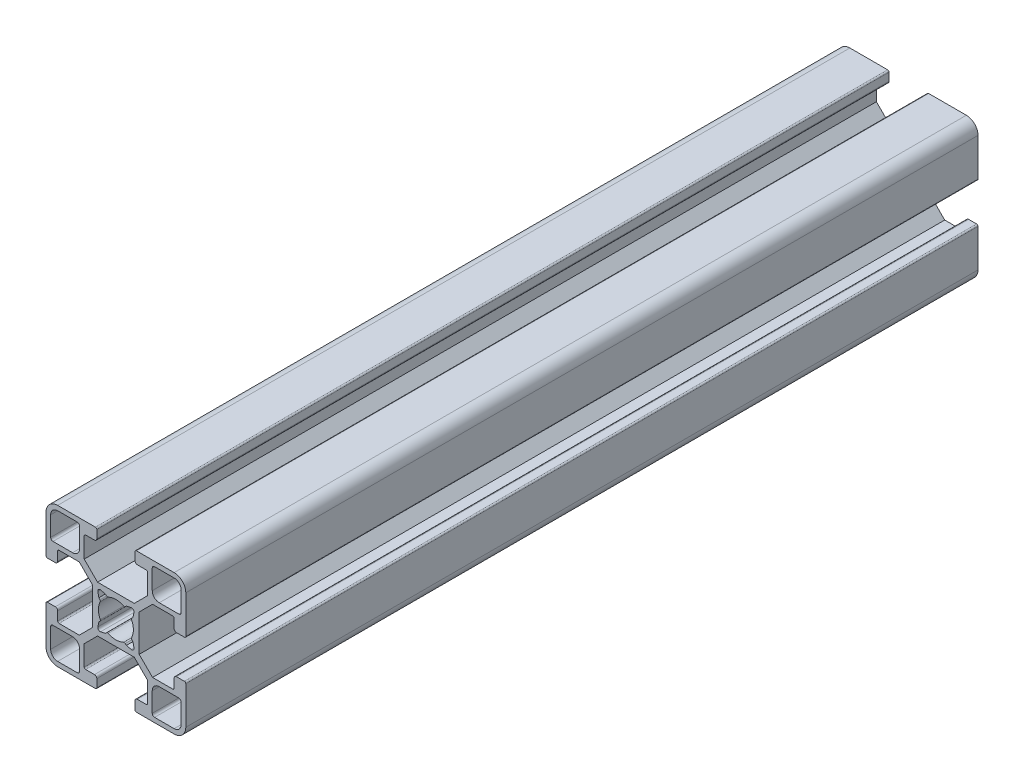
SolidWorks part; units mm, degrees
ref_plane "Front Plane" through (0, 0, 0) normal (0, 0, 1) x (1, 0, 0)
ref_plane "Top Plane" through (0, 0, 0) normal (0, 1, 0) x (1, 0, 0)
ref_plane "Right Plane" through (0, 0, 0) normal (1, 0, 0) x (0, 0, -1)
sketch "Sketch1" plane through (0, 0, 0) normal (0, 0, 1) x (1, 0, 0)
  line L0 (18.8789, 11.7141) -> (18.6573, 12.7569)
  line L1 (11.3427, 17.2431) -> (11.1211, 18.2859)
  line L2 (12.9949, 18.4193) -> (12.7569, 18.6573)
  line L3 (21.8, 7.1394) -> (18.9393, 10)
  line L4 (22.8607, 8.2) -> (20, 11.0607)
  line L5 (11.5807, 17.0051) -> (11.3427, 17.2431)
  line L6 (17.2431, 11.3427) -> (17.0051, 11.5806)
  line L7 (10, 18.9393) -> (7.1393, 21.8)
  line L8 (11.0607, 20) -> (8.2, 22.8607)
  line L9 (18.6573, 12.7569) -> (18.4193, 12.9948)
  line L10 (18.2859, 11.1211) -> (17.2431, 11.3427)
  line L11 (12.7569, 18.6573) -> (11.7141, 18.8789)
  line L12 (2.5, 0) -> (10.6, 0)
  line L13 (19.4, 0) -> (27.5, 0)
  line L14 (23.3, 1) -> (27.5, 1)
  line L15 (2.5, 1) -> (6.7, 1)
  line L16 (8.5, 2.5) -> (10.4, 2.5)
  line L17 (19.6, 2.5) -> (21.5, 2.5)
  line L18 (24.3, 7.2) -> (28.5, 7.2)
  line L19 (1.5, 7.2) -> (5.7, 7.2)
  line L20 (2.8, 8.2) -> (7.1393, 8.2)
  line L21 (22.8607, 8.2) -> (27.2, 8.2)
  line L22 (11.0607, 10) -> (18.9393, 10)
  line L23 (0.3, 10.9) -> (2, 10.9)
  line L24 (28, 10.9) -> (29.7, 10.9)
  line L25 (0.3, 19.1) -> (2, 19.1)
  line L26 (28, 19.1) -> (29.7, 19.1)
  line L27 (11.0607, 20) -> (18.9393, 20)
  line L28 (2.8, 21.8) -> (7.1393, 21.8)
  line L29 (22.8607, 21.8) -> (27.2, 21.8)
  line L30 (1.5, 22.8) -> (5.7, 22.8)
  line L31 (24.3, 22.8) -> (28.5, 22.8)
  line L32 (19.6, 27.5) -> (21.5, 27.5)
  line L33 (8.5, 27.5) -> (10.4, 27.5)
  line L34 (2.5, 29) -> (6.7, 29)
  line L35 (23.3, 29) -> (27.5, 29)
  line L36 (19.4, 30) -> (27.5, 30)
  line L37 (2.5, 30) -> (10.6, 30)
  line L38 (11.7141, 11.1211) -> (12.7569, 11.3427)
  line L39 (17.2431, 18.6573) -> (18.2859, 18.8789)
  line L40 (18.4194, 17.0051) -> (18.6573, 17.2431)
  line L41 (8.2, 7.1393) -> (11.0607, 10)
  line L42 (7.1393, 8.2) -> (10, 11.0607)
  line L43 (12.7569, 11.3427) -> (12.9949, 11.5806)
  line L44 (11.3427, 12.7569) -> (11.5807, 12.9949)
  line L45 (20, 18.9393) -> (22.8607, 21.8)
  line L46 (18.9393, 20) -> (21.8, 22.8607)
  line L47 (17.0051, 18.4193) -> (17.2431, 18.6573)
  line L48 (11.1211, 11.7141) -> (11.3427, 12.7569)
  line L49 (18.6573, 17.2431) -> (18.8789, 18.2859)
  line L50 (0, 19.4) -> (0, 27.5)
  line L51 (0, 2.5) -> (0, 10.6)
  line L52 (1, 23.3) -> (1, 27.5)
  line L53 (1, 2.5) -> (1, 6.7)
  line L54 (2.5, 8.5) -> (2.5, 10.4)
  line L55 (2.5, 19.6) -> (2.5, 21.5)
  line L56 (7.2, 24.3) -> (7.2, 28.5)
  line L57 (7.2, 1.5) -> (7.2, 5.7)
  line L58 (8.2, 2.8) -> (8.2, 7.1393)
  line L59 (8.2, 22.8607) -> (8.2, 27.2)
  line L60 (10, 11.0607) -> (10, 18.9393)
  line L61 (10.9, 0.3) -> (10.9, 2)
  line L62 (10.9, 28) -> (10.9, 29.7)
  line L63 (19.1, 0.3) -> (19.1, 2)
  line L64 (19.1, 28) -> (19.1, 29.7)
  line L65 (20, 11.0607) -> (20, 18.9393)
  line L66 (21.8, 2.8) -> (21.8, 7.1394)
  line L67 (21.8, 22.8607) -> (21.8, 27.2)
  line L68 (22.8, 24.3) -> (22.8, 28.5)
  line L69 (22.8, 1.5) -> (22.8, 5.7)
  line L70 (27.5, 8.5) -> (27.5, 10.4)
  line L71 (27.5, 19.6) -> (27.5, 21.5)
  line L72 (29, 23.3) -> (29, 27.5)
  line L73 (29, 2.5) -> (29, 6.7)
  line L74 (30, 2.5) -> (30, 10.6)
  line L75 (30, 19.4) -> (30, 27.5)
  arc A0 (0.3, 10.9) -> (0, 10.6) centre (0.3, 10.6) ccw
  arc A1 (0, 19.4) -> (0.3, 19.1) centre (0.3, 19.4) ccw
  arc A2 (1.5, 7.2) -> (1, 6.7) centre (1.5, 6.7) ccw
  arc A3 (1, 23.3) -> (1.5, 22.8) centre (1.5, 23.3) ccw
  arc A4 (2.5, 10.4) -> (2, 10.9) centre (2, 10.4) ccw
  arc A5 (2, 19.1) -> (2.5, 19.6) centre (2, 19.6) ccw
  arc A6 (1, 2.5) -> (2.5, 1) centre (2.5, 2.5) ccw
  arc A7 (0, 2.5) -> (2.5, 0) centre (2.5, 2.5) ccw
  arc A8 (2.5, 29) -> (1, 27.5) centre (2.5, 27.5) ccw
  arc A9 (2.5, 30) -> (0, 27.5) centre (2.5, 27.5) ccw
  arc A10 (2.5, 8.5) -> (2.8, 8.2) centre (2.8, 8.5) ccw
  arc A11 (2.8, 21.8) -> (2.5, 21.5) centre (2.8, 21.5) ccw
  arc A12 (7.2, 5.7) -> (5.7, 7.2) centre (5.7, 5.7) ccw
  arc A13 (5.7, 22.8) -> (7.2, 24.3) centre (5.7, 24.3) ccw
  arc A14 (6.7, 1) -> (7.2, 1.5) centre (6.7, 1.5) ccw
  arc A15 (7.2, 28.5) -> (6.7, 29) centre (6.7, 28.5) ccw
  arc A16 (8.2, 2.8) -> (8.5, 2.5) centre (8.5, 2.8) ccw
  arc A17 (8.5, 27.5) -> (8.2, 27.2) centre (8.5, 27.2) ccw
  arc A18 (10.9, 2) -> (10.4, 2.5) centre (10.4, 2) ccw
  arc A19 (10.4, 27.5) -> (10.9, 28) centre (10.4, 28) ccw
  arc A20 (10.6, 0) -> (10.9, 0.3) centre (10.6, 0.3) ccw
  arc A21 (10.9, 29.7) -> (10.6, 30) centre (10.6, 29.7) ccw
  arc A22 (11.5807, 12.9949) -> (11.6375, 13.3398) centre (11.3685, 13.207) ccw
  arc A23 (11.6375, 16.6602) -> (11.5807, 17.0051) centre (11.3685, 16.793) ccw
  arc A24 (11.1211, 11.7141) -> (11.7141, 11.1211) centre (11.6102, 11.6102) ccw
  arc A25 (11.7141, 18.8789) -> (11.1211, 18.2859) centre (11.6102, 18.3898) ccw
  arc A26 (13.3398, 11.6375) -> (12.9949, 11.5806) centre (13.207, 11.3685) ccw
  arc A27 (12.9949, 18.4193) -> (13.3398, 18.3625) centre (13.207, 18.6315) ccw
  arc A28 (11.6375, 16.6602) -> (11.6375, 13.3398) centre (15, 15) ccw
  arc A29 (16.6602, 18.3625) -> (13.3398, 18.3625) centre (15, 15) ccw
  arc A30 (18.3625, 13.3398) -> (18.3625, 16.6602) centre (15, 15) ccw
  arc A31 (13.3398, 11.6375) -> (16.6602, 11.6375) centre (15, 15) ccw
  arc A32 (17.0051, 11.5806) -> (16.6602, 11.6375) centre (16.793, 11.3685) ccw
  arc A33 (16.6602, 18.3625) -> (17.0051, 18.4193) centre (16.793, 18.6315) ccw
  arc A34 (18.2859, 11.1211) -> (18.8789, 11.7141) centre (18.3898, 11.6102) ccw
  arc A35 (18.8789, 18.2859) -> (18.2859, 18.8789) centre (18.3898, 18.3898) ccw
  arc A36 (18.3625, 13.3398) -> (18.4193, 12.9948) centre (18.6315, 13.207) ccw
  arc A37 (18.4194, 17.0051) -> (18.3625, 16.6602) centre (18.6315, 16.793) ccw
  arc A38 (19.1, 0.3) -> (19.4, 0) centre (19.4, 0.3) ccw
  arc A39 (19.4, 30) -> (19.1, 29.7) centre (19.4, 29.7) ccw
  arc A40 (19.6, 2.5) -> (19.1, 2) centre (19.6, 2) ccw
  arc A41 (19.1, 28) -> (19.6, 27.5) centre (19.6, 28) ccw
  arc A42 (21.5, 2.5) -> (21.8, 2.8) centre (21.5, 2.8) ccw
  arc A43 (21.8, 27.2) -> (21.5, 27.5) centre (21.5, 27.2) ccw
  arc A44 (22.8, 1.5) -> (23.3, 1) centre (23.3, 1.5) ccw
  arc A45 (23.3, 29) -> (22.8, 28.5) centre (23.3, 28.5) ccw
  arc A46 (24.3, 7.2) -> (22.8, 5.7) centre (24.3, 5.7) ccw
  arc A47 (22.8, 24.3) -> (24.3, 22.8) centre (24.3, 24.3) ccw
  arc A48 (27.2, 8.2) -> (27.5, 8.5) centre (27.2, 8.5) ccw
  arc A49 (27.5, 21.5) -> (27.2, 21.8) centre (27.2, 21.5) ccw
  arc A50 (27.5, 1) -> (29, 2.5) centre (27.5, 2.5) ccw
  arc A51 (27.5, 0) -> (30, 2.5) centre (27.5, 2.5) ccw
  arc A52 (29, 27.5) -> (27.5, 29) centre (27.5, 27.5) ccw
  arc A53 (30, 27.5) -> (27.5, 30) centre (27.5, 27.5) ccw
  arc A54 (28, 10.9) -> (27.5, 10.4) centre (28, 10.4) ccw
  arc A55 (27.5, 19.6) -> (28, 19.1) centre (28, 19.6) ccw
  arc A56 (29, 6.7) -> (28.5, 7.2) centre (28.5, 6.7) ccw
  arc A57 (28.5, 22.8) -> (29, 23.3) centre (28.5, 23.3) ccw
  arc A58 (30, 10.6) -> (29.7, 10.9) centre (29.7, 10.6) ccw
  arc A59 (29.7, 19.1) -> (30, 19.4) centre (29.7, 19.4) ccw
extrude "Boss-Extrude1" add sketch "Sketch1" along normal mid plane 170
equation "\"LENGTH\"=500"
